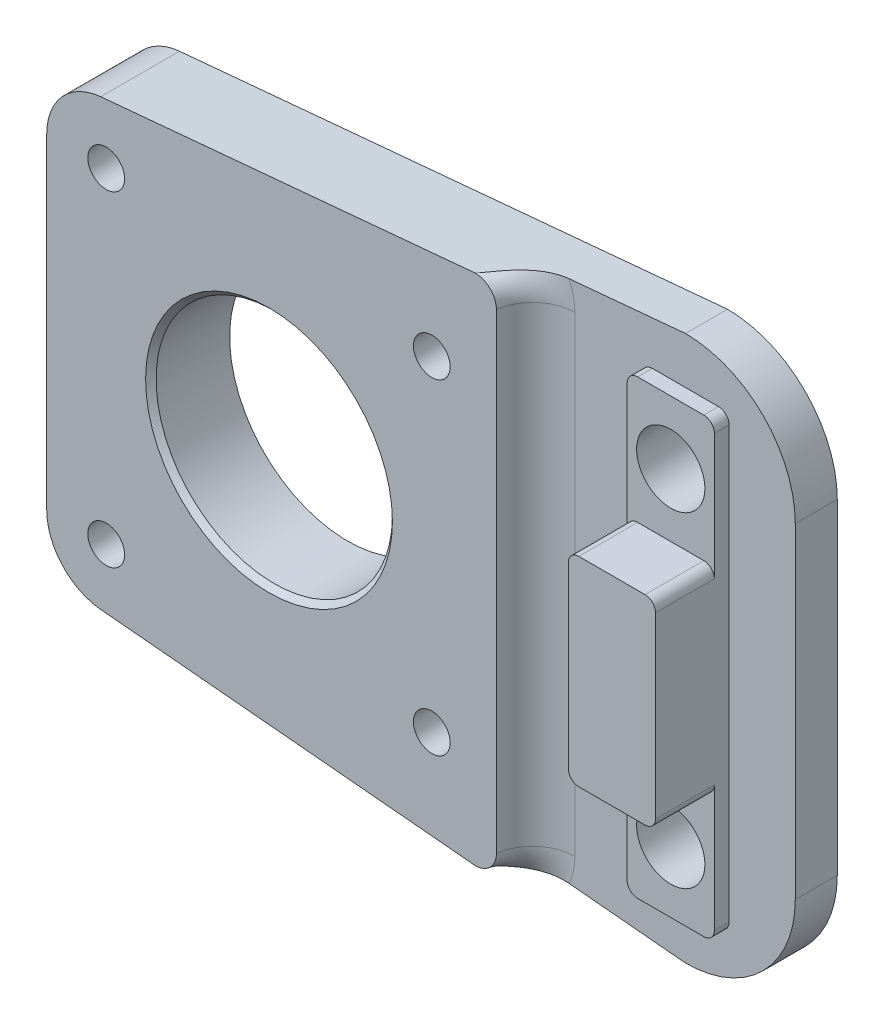
SolidWorks part; units mm, degrees
ref_plane "Спереди" through (0, 0, 0) normal (0, 0, 1) x (1, 0, 0)
ref_plane "Сверху" through (0, 0, 0) normal (0, 1, 0) x (1, 0, 0)
ref_plane "Справа" through (0, 0, 0) normal (1, 0, 0) x (0, 0, -1)
sketch "Эскиз1" plane through (0, 0, 0) normal (0, 0, 1) x (1, 0, 0)
  line L0 (-37.3089, 15.581) -> (-37.3089, -15.419)
  line L1 (20.006, -25.8742) -> (-32.1645, -21.0599)
  line L2 (-31.644, -15.419) -> (-31.644, 15.581) construction
  line L3 (15.856, -9.419) -> (24.156, -9.419)
  line L4 (-16.144, 0.081) -> (-52.4127, 0.081) construction
  line L5 (15.856, -9.419) -> (15.856, 9.581)
  line L6 (15.856, 9.581) -> (24.156, 9.581)
  line L7 (24.156, -9.419) -> (24.156, 9.581)
  line L8 (15.856, -9.419) -> (24.156, 9.581) construction
  line L9 (20.006, 26.5168) -> (20.006, -22.9876) construction
  line L10 (30.4613, 15.581) -> (30.4613, -15.419)
  line L11 (20.006, 26.0363) -> (-32.1645, 21.222)
  line L12 (20.006, -25.8742) -> (5.506, -24.5362)
  line L13 (5.506, -24.5362) -> (5.506, 24.6982)
  line L14 (15.856, 9.581) -> (24.156, -9.419) construction
  line L15 (15.856, -21.419) -> (24.156, -21.419)
  line L16 (15.856, -21.419) -> (15.856, 21.581)
  line L17 (15.856, 21.581) -> (24.156, 21.581)
  line L18 (24.156, -21.419) -> (24.156, 21.581)
  line L19 (15.856, -21.419) -> (24.156, 21.581) construction
  line L20 (15.856, 21.581) -> (24.156, -21.419) construction
  line L21 (-31.644, 15.581) -> (-0.644, 15.581) construction
  line L22 (-0.644, 15.581) -> (-0.644, -15.419) construction
  line L23 (-0.644, -15.419) -> (-31.644, -15.419) construction
  line L24 (-31.644, -15.419) -> (-0.644, 15.581) construction
  line L25 (-16.144, 0.081) -> (37.4151, 0.081) construction
  circle A0 centre (-31.644, 15.581) radius 1.75
  circle A1 centre (-0.644, 15.581) radius 1.75
  circle A2 centre (-31.644, -15.419) radius 1.75
  circle A3 centre (-0.644, -15.419) radius 1.75
  circle A4 centre (-16.144, 0.081) radius 11.25
  arc A5 (-37.3089, 15.581) -> (-32.1645, 21.222) centre (-31.644, 15.581) cw
  arc A6 (-37.3089, -15.419) -> (-32.1645, -21.0599) centre (-31.644, -15.419) ccw
  circle A9 centre (20.006, 15.581) radius 3.25
  circle A10 centre (20.006, -15.419) radius 3.25
  arc A11 (30.4613, 15.581) -> (20.006, 26.0363) centre (20.006, 15.581) ccw
  arc A12 (20.006, -25.8742) -> (30.4613, -15.419) centre (20.006, -15.419) ccw
  point P13 (-37.3089, 0.081)
  point P15 (20.006, 0.081)
  point P33 (20.006, 0.081)
  point P44 (5.506, 0.081)
  dimension "D2" = 6.5
  dimension "D1" = 6.5
  dimension "D5" = 3.5
  dimension "D6" = 3.5
  dimension "D7" = 3.5
  dimension "D8" = 22.5
  dimension "D9" = 3.5
  dimension "D4" = 10.4552
  dimension "D3" = 6
  dimension "D10" = 8.3
  dimension "D11" = 14.5
  dimension "D12" = 6
  dimension "D13" = 31
  dimension "D14" = 31
extrude "Бобышка-Вытянуть1" add sketch "Эскиз1" along normal blind 4 contours L12 L13 L11 L0 A6 A0 A1 A2 A3 A4 | L12 A12 L10 A11 L11 L13 L7 L3 L5 L6 A9 A10 | L3 L7 L6 L5 | L6 L18 L17 L16 A9 | L15 L18 L3 L16 A10 region at (-35.3476, 18.9586, 0) region at (12.809, 24.7937, 0) region at (20.006, 0.081, 0) region at (20.006, -9.5649, 0) region at (16.002, 15.581, 0)
extrude "Бобышка-Вытянуть2" add sketch "Эскиз1<3>" along normal blind 7.5 contours L12 L13 L11 L0 A6 A0 A1 A2 A3 A4 region at (-35.3476, 18.9586, 0)
sketch "Эскиз1<3>" plane through (0, 0, 0) normal (0, 0, 1) x (1, 0, 0) same geometry as "Эскиз1"
extrude "Бобышка-Вытянуть3" add sketch "Эскиз1<4>" along normal blind 11 contours L3 L7 L6 L5 region at (20.006, 0.081, 0)
sketch "Эскиз1<4>" plane through (0, 0, 0) normal (0, 0, 1) x (1, 0, 0) same geometry as "Эскиз1"
fillet "Скругление1" radius 2 2 edges at (5.506, 24.6982, 5.75) (5.506, -24.5362, 5.75)
fillet "Скругление3" radius 4 3 edges at (4.8537, 23.9829, 4) (5.506, 0.081, 4) (4.8537, -23.8209, 4)
extrude "Бобышка-Вытянуть4" add sketch "Эскиз1<5>" along normal blind 5.4 contours L6 L18 L17 L16 A9 | L15 L18 L3 L16 A10 | L3 L7 L6 L5 region at (20.006, 0.081, 0) region at (20.006, -9.5649, 0) region at (16.002, 15.581, 0)
sketch "Эскиз1<5>" plane through (0, 0, 0) normal (0, 0, 1) x (1, 0, 0) same geometry as "Эскиз1"
fillet "Скругление2" radius 1 8 edges at (15.856, -9.419, 8.2) (15.856, 9.581, 8.2) (24.156, 9.581, 8.2) (24.156, -9.419, 8.2) (24.156, -21.419, 4.7) (15.856, -21.419, 4.7) (15.856, 21.581, 4.7) (24.156, 21.581, 4.7)
chamfer "Фаска1" distance 0.5 angle 45 1 edges at (-4.894, 0.081, 7.5)
